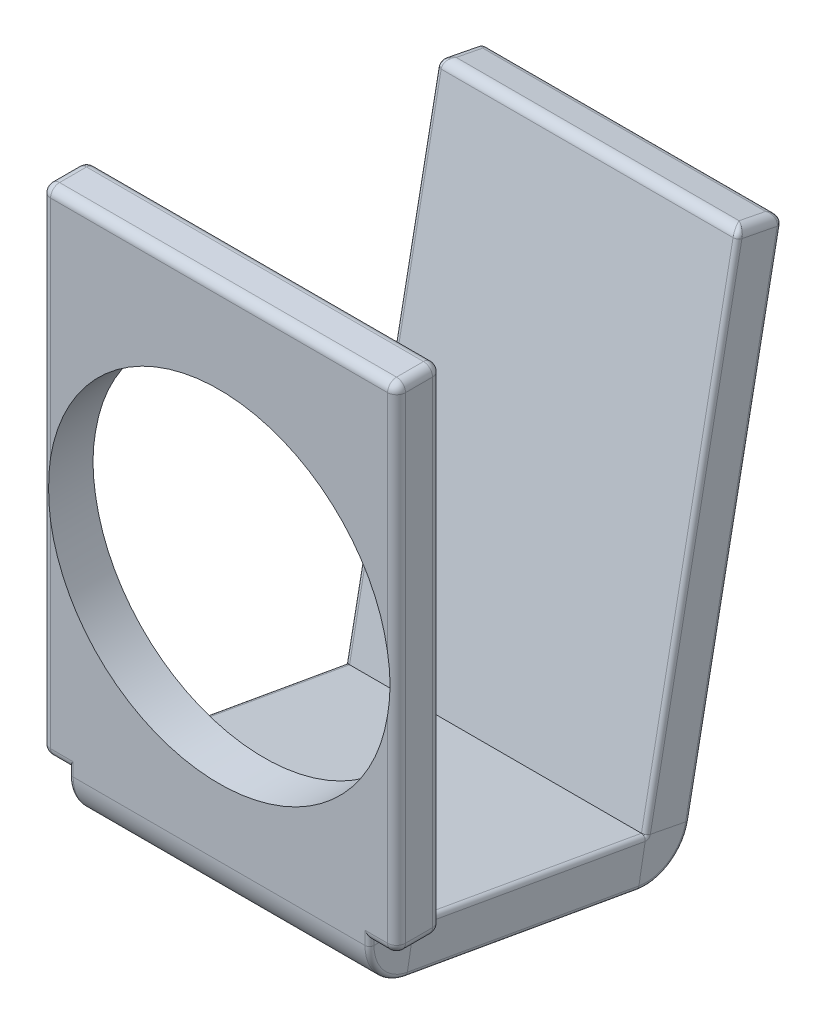
SolidWorks part; units mm, degrees
ref_plane "Front Plane" through (0, 0, 0) normal (0, 0, 1) x (1, 0, 0)
ref_plane "Top Plane" through (0, 0, 0) normal (0, 1, 0) x (1, 0, 0)
ref_plane "Right Plane" through (0, 0, 0) normal (1, 0, 0) x (0, 0, -1)
sketch "Path" plane through (0, 0, 0) normal (1, 0, 0) x (0, 0, -1)
  line L0 (-0.25, 2.7563) -> (-0.25, -2.7972)
  line L1 (-0.0436, -3.0433) -> (2.5328, -3.5)
  line L2 (2.8218, -3.3017) -> (3.8603, 2.0273)
  line L3 (-1.5, -3.5) -> (5, -3.5) construction
  line L5 (0, 1.6) -> (0, 3)
  line L6 (0, 1.6) -> (0, 3) construction
  arc A0 (2.5328, -3.5) -> (2.8218, -3.3017) centre (2.5764, -3.2538) ccw
  arc A1 (-0.25, -2.7972) -> (-0.0436, -3.0433) centre (0, -2.7972) ccw
  dimension "D1" = 0.25
  dimension "D3" = 0.25
  dimension "D2" = 0.25
  dimension "D4" = 4.1103
  dimension "D5" = 5.329
  dimension "D6" = 2.6166
  dimension "D7" = 4.1503
ref_plane "Clip Starting Plane" through (0, 2.7563, 0) normal (0, -1, 0) x (-1, 0, 0)
sketch "Clip Profile" plane through (0, 2.7563, 0) normal (0, -1, 0) x (1, 0, 0)
  line L1 (0, 0.0436) -> (0, 0.25) construction
  line L2 (1.6241, 0.5) -> (-1.6241, 0.5)
  line L3 (1.6741, 0.45) -> (1.6741, 0.05)
  line L4 (1.6241, 0) -> (-1.6241, 0)
  line L5 (-1.6741, 0.45) -> (-1.6741, 0.05)
  line L6 (1.6741, 0.5) -> (-1.6741, 0) construction
  line L7 (1.6741, 0) -> (-1.6741, 0.5) construction
  line L8 (1.75, -0.25) -> (1.75, -4.5) construction
  line L9 (1.75, -2.375) -> (1.75, 1.4296) construction
  arc A0 (1.6741, 0.05) -> (1.6241, 0) centre (1.6241, 0.05) cw
  arc A1 (1.6241, 0.5) -> (1.6741, 0.45) centre (1.6241, 0.45) cw
  arc A2 (-1.6241, 0) -> (-1.6741, 0.05) centre (-1.6241, 0.05) cw
  arc A3 (-1.6241, 0.5) -> (-1.6741, 0.45) centre (-1.6241, 0.45) ccw
  point P2 (0, 0.25)
  dimension "D4" = 0.05
  dimension "D1" = 0.5
  dimension "D2" = 0.0759
  dimension "D3" = 0.25
sweep "Sweep1" add profiles "Clip Profile" path "Path"
sketch "Sketch4" plane through (0, 0, 0.5) normal (0, 0, 1) x (1, 0, 0)
  line L0 (1.975, -2.75) -> (1.975, 3) construction
  line L1 (-1.975, -2.75) -> (-1.975, 3) construction
  line L2 (1.975, -2.75) -> (1.975, 2.7563)
  line L3 (-1.975, -2.75) -> (-1.975, 2.7563)
  line L4 (-1.6241, 2.7563) -> (-1.6241, -2.7972)
  line L5 (-1.6241, -2.7972) -> (1.6241, -2.7972)
  line L6 (1.6241, -2.7972) -> (1.6241, 2.7563)
  line L7 (1.6241, 2.7563) -> (-1.6241, 2.7563)
  line L11 (1.975, 2.7563) -> (-1.975, 2.7563)
  line L12 (-1.975, -2.75) -> (1.975, -2.75)
  dimension "D1" = 0
extrude "Boss-Extrude1" add sketch "Sketch4" against normal up to surface (0.5 mm away) up to face at (0, -0.0204, 0)
sketch "Sketch5" plane through (0, 0, 0.5) normal (0, 0, 1) x (1, 0, 0)
  circle A0 centre (0, -0.15) radius 1.9 construction
  circle A1 centre (0, -0.15) radius 1.9
extrude "Cut-Extrude1" cut sketch "Sketch5" against normal up to next
fillet "Fillet1" radius 0.1 18 edges at (1.975, 0.0031, 0.5) (1.975, 0.0031, 0) (1.975, -2.75, 0.25) (-1.975, 0.0031, 0.5) (-1.975, -2.75, 0.25) (-1.975, 0.0031, 0) (-1.975, 2.7563, 0.25) (0, 2.7563, 0) (1.975, 2.7563, 0.25) (0, 2.7563, 0.5) (0, 2.0752, -3.6149) (-1.6594, 2.0724, -3.6293) (-1.6741, 2.0273, -3.8603) (-1.6594, 1.9823, -4.0913) (0, 1.9795, -4.1057) (1.6594, 1.9823, -4.0913) (1.6741, 2.0273, -3.8603) (1.6594, 2.0724, -3.6293)
fillet "Fillet2" radius 0.1 8 edges at (-1.9457, -2.7207, 0.0293) (-1.9457, -2.7207, 0.4707) (1.9457, -2.7207, 0.0293) (1.9457, -2.7207, 0.4707) (-1.7495, -2.75, 0) (-1.7495, -2.75, 0.5) (1.7495, -2.75, 0) (1.7495, -2.75, 0.5)
